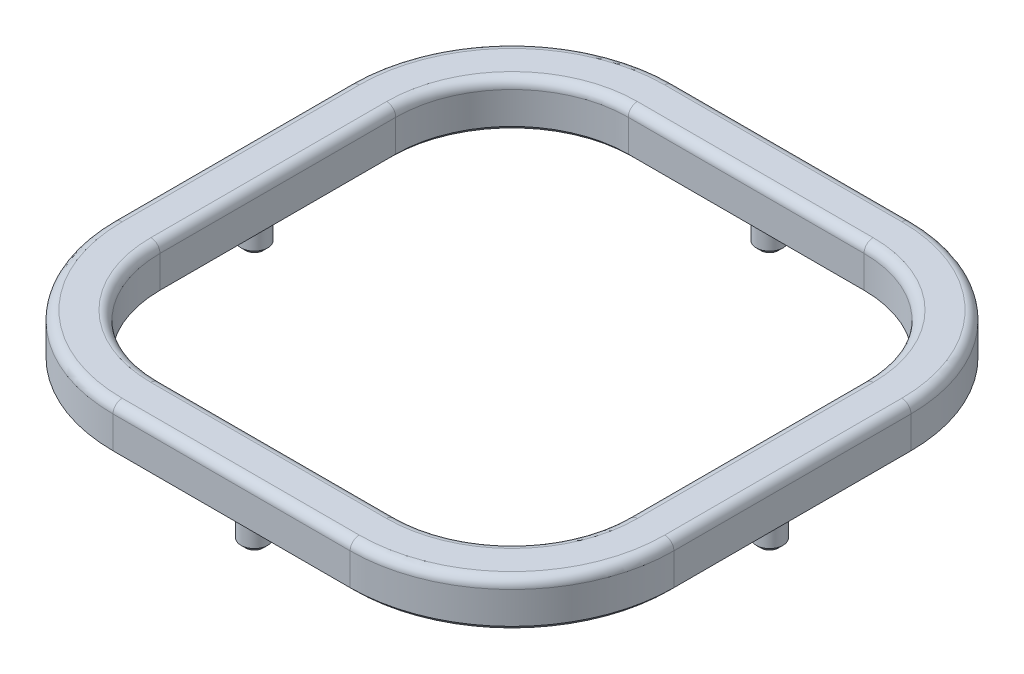
SolidWorks part; units mm, degrees
material "ABS"
ref_plane "Front" through (0, 0, 0) normal (0, 0, 1) x (1, 0, 0)
ref_plane "Top" through (0, 0, 0) normal (0, 1, 0) x (1, 0, 0)
ref_plane "Right" through (0, 0, 0) normal (1, 0, 0) x (0, 0, -1)
sketch "Эскиз1" plane through (0, 0, 0) normal (0, 1, 0) x (1, 0, 0)
  line L1 (25.85, -51.35) -> (-25.85, -51.35)
  line L2 (51.35, -25.85) -> (51.35, 25.85)
  line L3 (25.85, 51.35) -> (-25.85, 51.35)
  line L4 (-51.35, -25.85) -> (-51.35, 25.85)
  line L5 (51.35, -51.35) -> (-51.35, 51.35) construction
  line L6 (51.35, 51.35) -> (-51.35, -51.35) construction
  line L7 (56.5, -56.5) -> (-56.5, -56.5) construction
  line L8 (56.5, -56.5) -> (56.5, 56.5) construction
  line L9 (56.5, 56.5) -> (-56.5, 56.5) construction
  line L10 (-56.5, -56.5) -> (-56.5, 56.5) construction
  line L11 (56.5, -56.5) -> (-56.5, 56.5) construction
  line L12 (56.5, 56.5) -> (-56.5, -56.5) construction
  line L13 (26, -61.5) -> (-26, -61.5)
  line L14 (61.5, -26) -> (61.5, 26)
  line L15 (26, 61.5) -> (-26, 61.5)
  line L16 (-61.5, -26) -> (-61.5, 26)
  line L17 (61.5, -61.5) -> (-61.5, 61.5) construction
  line L18 (61.5, 61.5) -> (-61.5, -61.5) construction
  circle A9 centre (0, 56.5) radius 2.925
  circle A10 centre (-56.5, 0) radius 2.925
  circle A11 centre (0, -56.5) radius 2.925
  circle A12 centre (56.5, 0) radius 2.925
  arc A13 (-26, 61.5) -> (-61.5, 26) centre (-26, 26) ccw
  arc A14 (61.5, 26) -> (26, 61.5) centre (26, 26) ccw
  arc A15 (26, -61.5) -> (61.5, -26) centre (26, -26) ccw
  arc A16 (-61.5, -26) -> (-26, -61.5) centre (-26, -26) ccw
  arc A17 (-25.85, 51.35) -> (-51.35, 25.85) centre (-25.85, 25.85) ccw
  arc A18 (51.35, 25.85) -> (25.85, 51.35) centre (25.85, 25.85) ccw
  arc A19 (25.85, -51.35) -> (51.35, -25.85) centre (25.85, -25.85) ccw
  arc A20 (-51.35, -25.85) -> (-25.85, -51.35) centre (-25.85, -25.85) ccw
  point P0 (0, 0)
  point P5 (0, 0)
  point P10 (0, 0)
  dimension "D1" = 123
  dimension "D2" = 123
  dimension "D3" = 102.7
  dimension "D4" = 102.7
  dimension "D5" = 113
  dimension "D6" = 113
  dimension "D7" = 5.85
  dimension "D8" = 5.85
  dimension "D9" = 5.85
  dimension "D10" = 5.85
  dimension "D11" = 35.5
  dimension "D12" = 35.5
  dimension "D13" = 35.5
  dimension "D14" = 35.5
  dimension "D15" = 25.5
  dimension "D16" = 25.5
  dimension "D17" = 25.5
  dimension "D18" = 25.5
extrude "Бобышка-Вытянуть1" add sketch "Эскиз1" along normal blind 10 contours A16 L13 A15 L14 A14 L15 A13 L16 | A20 L1 A19 L2 A18 L3 A17 L4
extrude "Бобышка-Вытянуть2" add sketch "Эскиз1<7>" against normal blind 6 contours A10 | A9 | A11 | A12
sketch "Эскиз1<7>" plane through (0, 0, 0) normal (0, 1, 0) x (1, 0, 0) same geometry as "Эскиз1"
chamfer "Фаска1" distance 1 angle 45 20 edges at (56.5, -6, 2.925) (0, -6, -53.575) (-56.5, -6, 2.925) (0, -6, 59.425) (43.8812, 0, -43.8812) (0, 0, -51.35) (51.35, 0, 0) (-43.8812, 0, -43.8812) (43.8812, 0, 43.8812) (-51.35, 0, 0) (0, 0, 51.35) (-43.8812, 0, 43.8812) (0, 0, -61.5) (51.1023, 0, -51.1023) (-51.1023, 0, -51.1023) (61.5, 0, 0) (-61.5, 0, 0) (51.1023, 0, 51.1023) (-51.1023, 0, 51.1023) (0, 0, 61.5)
fillet "Скругление1" radius 2 16 edges at (-51.35, 10, 0) (-43.8812, 10, -43.8812) (0, 10, -51.35) (43.8812, 10, -43.8812) (51.35, 10, 0) (43.8812, 10, 43.8812) (0, 10, 51.35) (51.1023, 10, 51.1023) (61.5, 10, 0) (51.1023, 10, -51.1023) (0, 10, -61.5) (-51.1023, 10, -51.1023) (-61.5, 10, 0) (-51.1023, 10, 51.1023) (-43.8812, 10, 43.8812) (0, 10, 61.5)
fillet "Скругление2" radius 0.4 4 edges at (0, 0, -53.575) (0, 0, 59.425) (-56.5, 0, 2.925) (56.5, 0, 2.925)
